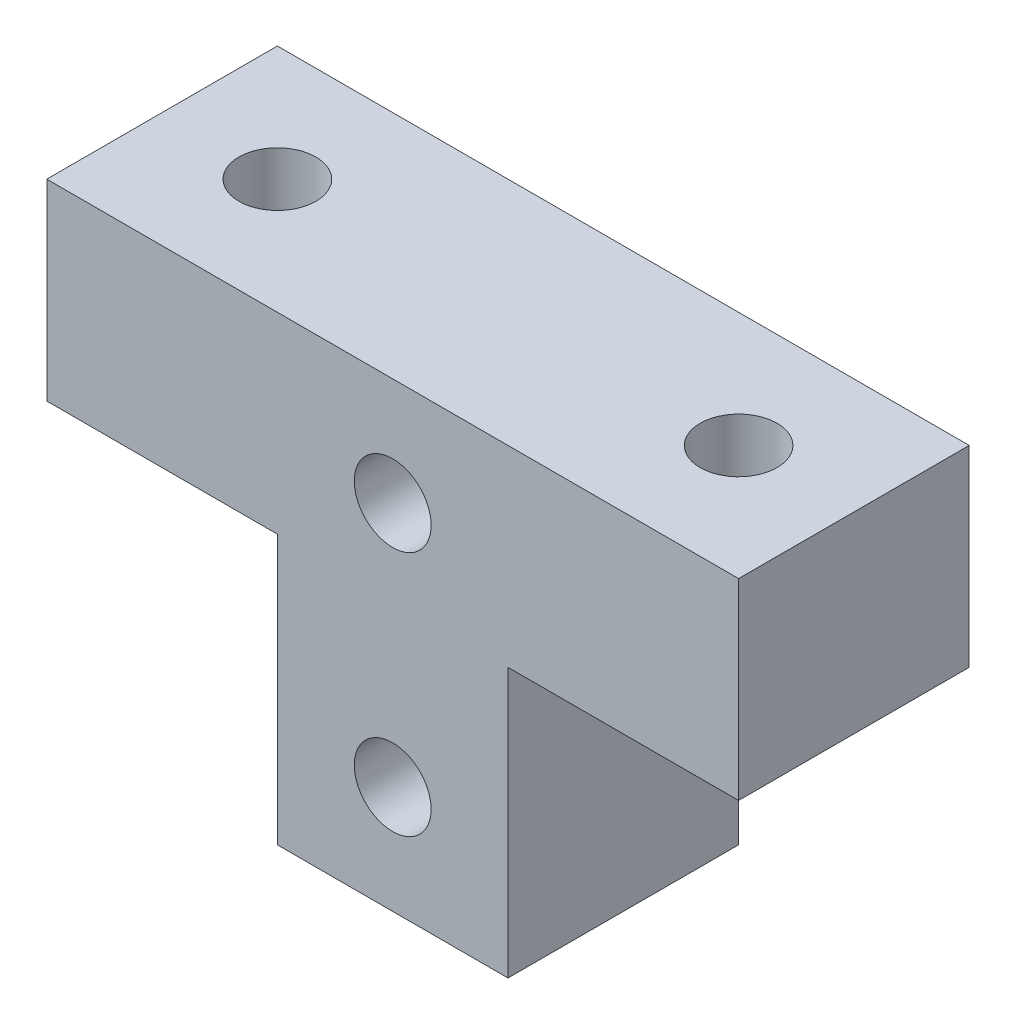
SolidWorks part; units mm, degrees
ref_plane "Front" through (0, 0, 0) normal (0, 0, 1) x (1, 0, 0)
ref_plane "Top" through (0, 0, 0) normal (0, 1, 0) x (1, 0, 0)
ref_plane "Right" through (0, 0, 0) normal (1, 0, 0) x (0, 0, -1)
sketch "Sketch1" plane through (0, 0, 0) normal (0, 0, 1) x (1, 0, 0)
  line L0 (0, 0) -> (22.2463, 0) construction
  line L1 (-28.575, 19.05) -> (28.575, 19.05)
  line L2 (19.05, 29.2913) -> (19.05, -10.8361) construction
  line L3 (9.525, 3.175) -> (19.05, 3.175)
  line L4 (28.575, 19.05) -> (28.575, 3.175)
  line L5 (19.05, 3.175) -> (28.575, 3.175)
  line L6 (0, 19.05) -> (0, -19.05) construction
  line L7 (-9.525, -19.05) -> (9.525, -19.05)
  line L8 (9.525, 3.175) -> (9.525, -19.05)
  line L9 (-9.525, 3.175) -> (-9.525, -19.05)
  line L10 (-9.525, 3.175) -> (-19.05, 3.175)
  line L11 (-19.05, 3.175) -> (-28.575, 3.175)
  line L12 (-28.575, 19.05) -> (-28.575, 3.175)
  dimension "D1" = 9.525
  dimension "D2" = 38.1
  dimension "D3" = 3.175
  dimension "D4" = 19.05
extrude "Boss-Extrude1" add sketch "Sketch1" against normal blind 19.05
hole_wizard "1/4 (0.25) Diameter Hole1" positions "Sketch2" profile "Sketch3" hole size "1/4" standard "ANSI Inch" end condition through all
sketch "Sketch2" plane through (0, 0, 0) normal (0, 0, 1) x (1, 0, 0)
  line L0 (0, 10.16) -> (0, -10.16) construction
  point P0 (0, 10.16)
  point P2 (0, -10.16)
  point P7 (0, 0)
  dimension "D1" = 20.32
sketch "Sketch3" plane through (0, 10.16, 0) normal (1, 0, 0) x (0, -1, 0)
  line L0 (0, 0) -> (0, 19.05)
  line L1 (0, 19.05) -> (3.175, 19.05)
  line L2 (3.175, 19.05) -> (3.175, 0)
  line L5 (3.175, 0) -> (0, 0)
  line L11 (0, -6.35) -> (0, 107.95) construction
  dimension "Thru Hole Dia." = 6.35
  dimension "Thru Hole Depth" = 19.05
hole_wizard "1/4 (0.25) Diameter Hole2" positions "Sketch4" profile "Sketch5" hole size "1/4" standard "ANSI Inch" end condition through all
sketch "Sketch4" plane through (0, 19.05, 0) normal (0, 1, 0) x (1, 0, 0)
  line L0 (-19.05, 9.525) -> (19.05, 9.525) construction
  line L4 (0, 0) -> (0, 19.05) construction
  line L5 (28.575, 19.05) -> (-28.575, 19.05) construction
  point P0 (-19.05, 9.525)
  point P2 (19.05, 9.525)
  point P25 (0, 0)
  point P26 (0, 0)
  point P27 (0, 9.525)
  point P28 (0, 9.525)
  point P29 (17.8393, 9.525)
  dimension "D1" = 38.1
sketch "Sketch5" plane through (-19.05, 19.05, -9.525) normal (1, 0, 0) x (0, 0, 1)
  line L0 (0, 0) -> (0, 38.1)
  line L1 (0, 38.1) -> (3.175, 38.1)
  line L2 (3.175, 38.1) -> (3.175, 0)
  line L5 (3.175, 0) -> (0, 0)
  line L11 (0, -6.35) -> (0, 107.95) construction
  dimension "Thru Hole Dia." = 6.35
  dimension "Thru Hole Depth" = 38.1
